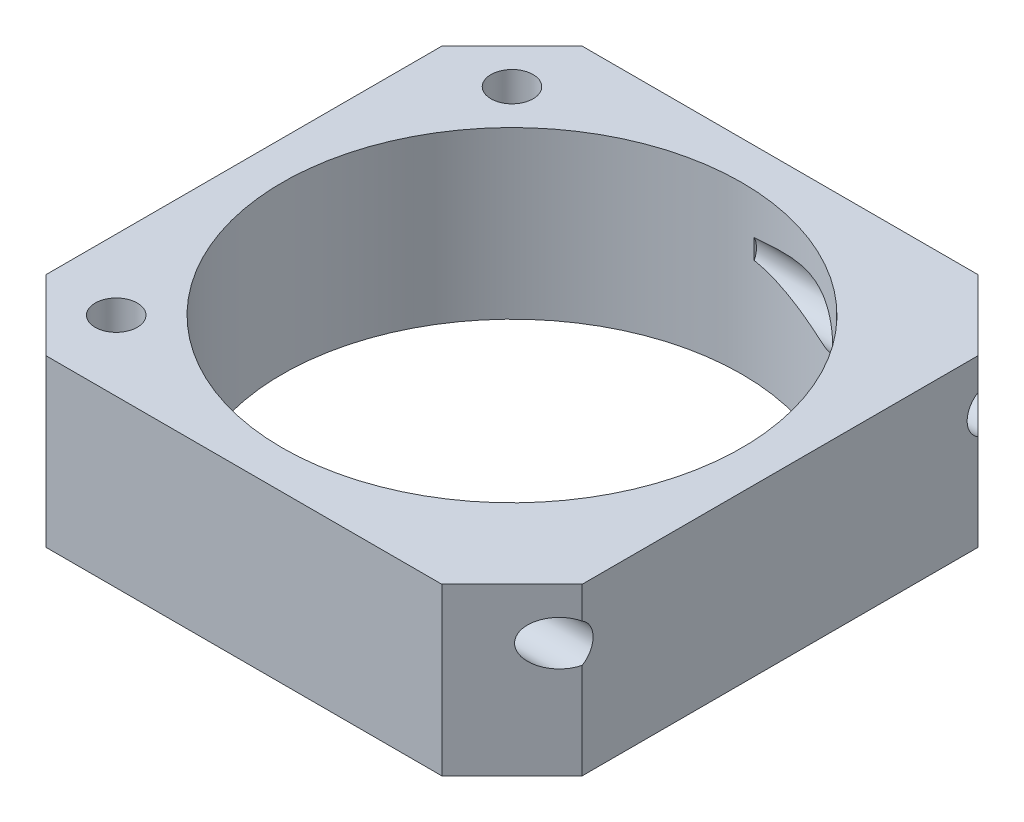
SolidWorks part; units mm, degrees
material "ABS"
ref_plane "Front Plane" through (0, 0, 0) normal (0, 0, 1) x (1, 0, 0)
ref_plane "Top Plane" through (0, 0, 0) normal (0, 1, 0) x (1, 0, 0)
ref_plane "Right Plane" through (0, 0, 0) normal (1, 0, 0) x (0, 0, -1)
sketch "Sketch1" plane through (0, 0, 0) normal (0, 1, 0) x (1, 0, 0)
  line L1 (0, 0) -> (42, 0)
  line L2 (0, 0) -> (0, 42)
  line L3 (0, 42) -> (42, 42)
  line L4 (42, 0) -> (42, 42)
  circle A0 centre (5.5, 36.5) radius 1.65
  circle A1 centre (5.5, 5.5) radius 1.65
  circle A4 centre (21, 21) radius 18
  point P16 (21, 21)
  dimension "D3" = 5.5
  dimension "D5" = 3.3
  dimension "D7" = 36
  dimension "D6" = 5.5
  dimension "D9" = 3.3
  dimension "D1" = 42
  dimension "D2" = 42
  dimension "D4" = 5.5
  dimension "D8" = 5.5
extrude "Boss-Extrude1" add sketch "Sketch1" along normal blind 13
chamfer "Chamfer1" distance 5.5 angle 45 4 edges at (42, 6.5, 0) (42, 6.5, -42) (0, 6.5, 0) (0, 6.5, -42)
sketch "Sketch3" plane through (42, 0, 0) normal (1, 0, 0) x (0, 0, -1)
  line L0 (5.5, 0) -> (36.5, 0) construction
  line L1 (42, 13) -> (42, 0) construction
  circle A0 centre (37.4, 9) radius 1.75
  dimension "D1" = 9
  dimension "D2" = 3.5
  dimension "D3" = 4.6
extrude "Cut-Extrude2" cut sketch "Sketch3" against normal blind 20
sketch "Sketch4" plane through (42, 0, 0) normal (1, 0, 0) x (0, 0, -1)
  line L0 (5.5, 0) -> (36.5, 0) construction
  line L1 (0, 0) -> (0, 13) construction
  circle A0 centre (4.6, 9) radius 1.75
  dimension "D1" = 9
  dimension "D3" = 3.5
  dimension "D2" = 4.6
extrude "Cut-Extrude3" cut sketch "Sketch4" against normal blind 20
